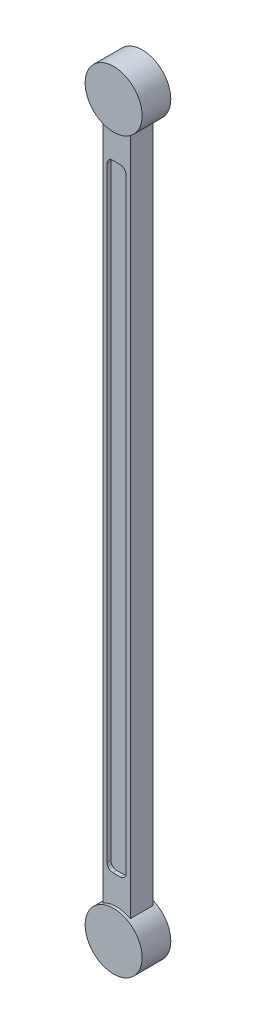
SolidWorks part; units mm, degrees
ref_plane "Front" through (0, 0, 0) normal (0, 0, 1) x (1, 0, 0)
ref_plane "Top" through (0, 0, 0) normal (0, 1, 0) x (1, 0, 0)
ref_plane "Right" through (0, 0, 0) normal (1, 0, 0) x (0, 0, -1)
sketch "Sketch1" plane through (-505.7052, -1154.2469, 0) normal (0, 0, 1) x (1, 0, 0)
  line L0 (486.1052, 2330.8055) -> (486.1052, 1197.687)
  line L1 (482.7052, 1195.9866) -> (482.7052, 2332.5059)
  line L2 (525.3052, 1197.687) -> (525.3052, 2330.8055)
  line L3 (528.7052, 2332.5059) -> (528.7052, 1195.9866)
  line L4 (486.2052, 1258.2462) -> (486.2052, 2330.7605)
  line L5 (489.7052, 2329.3546) -> (489.7052, 1258.2462)
  line L6 (499.7052, 2326.9677) -> (499.7052, 1258.2462)
  line L7 (511.7052, 1258.2462) -> (511.7052, 2326.9677)
  line L8 (521.7052, 1258.2462) -> (521.7052, 2329.3546)
  line L9 (525.2052, 2330.7605) -> (525.2052, 1258.2462)
  line L10 (486.2052, 1258.2462) -> (489.7052, 1258.2462)
  line L11 (525.2052, 1258.2462) -> (521.7052, 1258.2462)
  line L12 (511.7052, 1244.7462) -> (511.7052, 1248.2462)
  line L13 (499.7052, 1244.7462) -> (499.7052, 1248.2462)
  line L14 (511.7052, 1258.2462) -> (521.7052, 1258.2462)
  line L15 (499.7052, 1258.2462) -> (499.7052, 1248.2462)
  line L16 (511.7052, 1258.2462) -> (511.7052, 1248.2462)
  line L17 (499.7052, 1258.2462) -> (489.7052, 1258.2462)
  line L18 (499.7052, 1258.2462) -> (511.7052, 1258.2462)
  line L19 (511.7052, 1244.7462) -> (499.7052, 1244.7462)
  line L20 (499.7052, 1248.2462) -> (511.7052, 1248.2462)
  line L21 (499.7052, 2280.2462) -> (499.7052, 2283.7462)
  line L22 (489.7052, 2270.2462) -> (486.2052, 2270.2462)
  line L23 (511.7052, 2280.2462) -> (511.7052, 2283.7462)
  line L24 (521.7052, 2270.2462) -> (525.2052, 2270.2462)
  line L25 (521.7052, 2270.2462) -> (511.7052, 2270.2462)
  line L26 (511.7052, 2280.2462) -> (511.7052, 2270.2462)
  line L27 (499.7052, 2280.2462) -> (499.7052, 2270.2462)
  line L28 (489.7052, 2270.2462) -> (499.7052, 2270.2462)
  line L29 (499.7052, 2270.2462) -> (499.7052, 2244.371)
  line L30 (511.7052, 2270.2462) -> (499.7052, 2270.2462)
  line L31 (511.7052, 2257.0727) -> (511.7052, 2270.2462)
  line L32 (528.7052, 2277.7072) -> (528.7052, 2264.4354)
  line L33 (525.3052, 2264.9247) -> (525.3052, 2280.0122)
  line L34 (482.7052, 2234.556) -> (482.7052, 2308.8932)
  line L35 (486.1052, 2306.5882) -> (486.1052, 2236.519)
  line L36 (499.7052, 2283.7462) -> (511.7052, 2283.7462)
  line L37 (525.2052, 2270.2462) -> (525.2052, 2264.8669)
  line L38 (486.2052, 2236.5768) -> (486.2052, 2270.2462)
  line L39 (511.7052, 2280.2462) -> (499.7052, 2280.2462)
  line L40 (489.7052, 2270.2462) -> (489.7052, 2238.5975)
  line L41 (521.7052, 2262.8462) -> (521.7052, 2270.2462)
  line L42 (526.8021, 2265.7889) -> (527.2334, 2266.0379)
  line L43 (534.0206, 2434.9688) -> (531.9075, 2430.4373)
  circle A0 centre (505.7052, 1154.2462) radius 17.5
  circle A1 centre (505.7052, 1154.2462) radius 47.6577
  arc A2 (511.7052, 1244.7462) -> (525.2052, 1258.2462) centre (511.7052, 1258.2462) ccw
  arc A3 (486.2052, 1258.2462) -> (499.7052, 1244.7462) centre (499.7052, 1258.2462) ccw
  arc A4 (511.7052, 1248.2462) -> (521.7052, 1258.2462) centre (511.7052, 1258.2462) ccw
  arc A5 (489.7052, 1258.2462) -> (499.7052, 1248.2462) centre (499.7052, 1258.2462) ccw
  circle A6 centre (505.7052, 1154.2462) radius 22.5
  circle A7 centre (505.7052, 1154.2462) radius 27.5
  circle A8 centre (505.7052, 1154.2462) radius 16.5
  circle A9 centre (505.7052, 2374.2462) radius 47.6577
  circle A10 centre (505.7052, 2374.2462) radius 27.5
  circle A11 centre (505.7052, 2374.2462) radius 22.5
  arc A12 (499.7052, 2283.7462) -> (486.2052, 2270.2462) centre (499.7052, 2270.2462) ccw
  arc A13 (525.2052, 2270.2462) -> (511.7052, 2283.7462) centre (511.7052, 2270.2462) ccw
  arc A14 (521.7052, 2270.2462) -> (511.7052, 2280.2462) centre (511.7052, 2270.2462) ccw
  arc A15 (499.7052, 2280.2462) -> (489.7052, 2270.2462) centre (499.7052, 2270.2462) ccw
  circle A16 centre (505.7052, 2374.2462) radius 17.5
  circle A17 centre (505.7052, 2374.2462) radius 16.5
sketch "Sketch2" plane through (-505.7052, 0, 2556.1257) normal (0, 1, 0) x (1, 0, 0)
  line L0 (505.7052, 2532.1257) -> (505.7052, 2556.1257) construction
  line L1 (501.0475, 2580.6257) -> (549.0475, 2580.6257)
  line L2 (501.0475, 2580.6257) -> (501.0475, 2580.1257)
  line L3 (549.0475, 2580.1257) -> (549.0475, 2580.6257)
  line L4 (458.0475, 2575.1257) -> (458.0475, 2537.1257)
  line L5 (551.2498, 2580.1257) -> (463.0475, 2580.1257)
  line L6 (551.2498, 2532.1257) -> (551.434, 2532.1447)
  line L7 (551.434, 2532.1447) -> (551.6167, 2532.2017)
  line L8 (551.6167, 2532.2017) -> (551.7967, 2532.2961)
  line L9 (551.7967, 2532.2961) -> (551.9725, 2532.4272)
  line L10 (551.9725, 2532.4272) -> (552.1428, 2532.5942)
  line L11 (552.1428, 2532.5942) -> (552.3064, 2532.7956)
  line L12 (552.3064, 2532.7956) -> (552.4618, 2533.0299)
  line L13 (552.4618, 2533.0299) -> (552.6081, 2533.2955)
  line L14 (552.6081, 2533.2955) -> (552.744, 2533.5902)
  line L15 (552.744, 2533.5902) -> (552.8685, 2533.9118)
  line L16 (552.8685, 2533.9118) -> (552.9808, 2534.2578)
  line L17 (552.9808, 2534.2578) -> (553.0798, 2534.6257)
  line L18 (553.0798, 2534.6257) -> (553.1649, 2535.0126)
  line L19 (553.1649, 2535.0126) -> (553.2355, 2535.4156)
  line L20 (553.2355, 2535.4156) -> (553.2909, 2535.8316)
  line L21 (553.2909, 2535.8316) -> (553.3308, 2536.2575)
  line L22 (553.3308, 2536.2575) -> (553.3549, 2536.6899)
  line L23 (553.3549, 2536.6899) -> (553.3629, 2537.1257)
  line L24 (551.2498, 2532.1257) -> (463.0475, 2532.1257)
  line L25 (553.3629, 2575.1257) -> (458.0475, 2575.1257)
  line L26 (553.3629, 2575.1257) -> (553.3549, 2575.5615)
  line L27 (553.3549, 2575.5615) -> (553.3308, 2575.9939)
  line L28 (553.3308, 2575.9939) -> (553.2909, 2576.4198)
  line L29 (553.2909, 2576.4198) -> (553.2355, 2576.8358)
  line L30 (553.2355, 2576.8358) -> (553.1649, 2577.2388)
  line L31 (553.1649, 2577.2388) -> (553.0798, 2577.6257)
  line L32 (553.0798, 2577.6257) -> (552.9808, 2577.9936)
  line L33 (552.9808, 2577.9936) -> (552.8685, 2578.3396)
  line L34 (552.8685, 2578.3396) -> (552.744, 2578.6612)
  line L35 (552.744, 2578.6612) -> (552.6081, 2578.9559)
  line L36 (552.6081, 2578.9559) -> (552.4618, 2579.2215)
  line L37 (552.4618, 2579.2215) -> (552.3064, 2579.4558)
  line L38 (552.3064, 2579.4558) -> (552.1428, 2579.6572)
  line L39 (552.1428, 2579.6572) -> (551.9725, 2579.8242)
  line L40 (551.9725, 2579.8242) -> (551.7967, 2579.9553)
  line L41 (551.7967, 2579.9553) -> (551.6167, 2580.0497)
  line L42 (551.6167, 2580.0497) -> (551.434, 2580.1067)
  line L43 (551.434, 2580.1067) -> (551.2498, 2580.1257)
  line L44 (553.3629, 2537.1257) -> (553.3629, 2575.1257)
  line L45 (458.0475, 2537.1257) -> (553.3629, 2537.1257)
  line L46 (522.3697, 2530.8597) -> (522.8128, 2531.7094)
  line L47 (538.4272, 2528.1257) -> (522.8128, 2531.7094)
  line L48 (486.0475, 2524.2368) -> (486.4833, 2524.2516)
  line L49 (486.4833, 2524.2516) -> (486.9157, 2524.2959)
  line L50 (486.9157, 2524.2959) -> (487.3416, 2524.3693)
  line L51 (487.3416, 2524.3693) -> (487.7576, 2524.4713)
  line L52 (487.7576, 2524.4713) -> (488.1606, 2524.6012)
  line L53 (488.1606, 2524.6012) -> (488.5475, 2524.7578)
  line L54 (488.5475, 2524.7578) -> (488.9154, 2524.9401)
  line L55 (488.9154, 2524.9401) -> (489.2614, 2525.1466)
  line L56 (489.2614, 2525.1466) -> (489.583, 2525.3758)
  line L57 (489.583, 2525.3758) -> (489.8777, 2525.626)
  line L58 (489.8777, 2525.626) -> (490.1432, 2525.8951)
  line L59 (490.1432, 2525.8951) -> (490.3776, 2526.1813)
  line L60 (490.3776, 2526.1813) -> (490.579, 2526.4822)
  line L61 (490.579, 2526.4822) -> (490.7459, 2526.7956)
  line L62 (490.7459, 2526.7956) -> (490.8771, 2527.1192)
  line L63 (490.8771, 2527.1192) -> (490.9715, 2527.4504)
  line L64 (490.9715, 2527.4504) -> (491.0284, 2527.7868)
  line L65 (491.0284, 2527.7868) -> (491.0475, 2528.1257)
  line L66 (527.6129, 2528.1257) -> (496.0475, 2528.1257)
  line L67 (496.0475, 2528.1257) -> (491.0475, 2528.1257)
  line L68 (522.8128, 2531.7094) -> (522.552, 2532.1257)
  line L69 (538.4272, 2532.1257) -> (538.4272, 2528.1257)
  line L70 (496.0475, 2528.1257) -> (496.0475, 2532.1257)
  line L71 (458.0475, 2556.1257) -> (553.3629, 2556.1257) construction
  line L72 (505.7052, 2575.1257) -> (505.7052, 2700.0052) construction
  arc A0 (501.0475, 2580.6257) -> (502.984, 2581.1257) centre (501.0475, 2584.6257) ccw
  arc A1 (547.111, 2581.1257) -> (549.0475, 2580.6257) centre (549.0475, 2584.6257) ccw
  arc A2 (463.0475, 2580.1257) -> (458.0475, 2575.1257) centre (463.0475, 2575.1257) ccw
  arc A3 (458.0475, 2537.1257) -> (463.0475, 2532.1257) centre (463.0475, 2537.1257) ccw
  arc A4 (491.6106, 2532.2989) -> (486.0475, 2524.2368) centre (495.5173, 2523.6527) ccw
  arc A5 (522.3697, 2530.8597) -> (519.3677, 2532.1257) centre (513.1227, 2513.1257) ccw
  arc A6 (522.8128, 2531.7094) -> (520.3216, 2532.3493) centre (513.0839, 2499.0025) ccw
sketch "Sketch3" plane through (0, 0, 0) normal (0, 0, 1) x (1, 0, 0)
  line L0 (23, 1178.259) -> (23, 41.7397)
  line L2 (-23, 1178.259) -> (-23, 41.7397)
  arc A0 (-23, 41.7397) -> (23, 41.7397) centre (0, 0) ccw
  arc A1 (23, 1178.259) -> (-23, 1178.259) centre (0, 1219.9994) ccw
extrude "Extrude1" add sketch "Sketch3" against normal up to vertex and the other way blind 19.05 up to point (-47.6577, 0, -19)
sketch "Sketch4" plane through (0, 0, 19.05) normal (0, 0, 1) x (1, 0, 0)
  line L0 (-6, 93.9994) -> (6, 93.9994) construction
  line L1 (6, 1125.9994) -> (-6, 1125.9994) construction
  line L5 (15.888, 1178.259) -> (15.888, 41.7397)
  line L6 (15.888, 1116.3474) -> (15.888, 103.6514)
  line L7 (-6.236, 1125.9994) -> (6.236, 1125.9994)
  line L8 (-15.888, 41.7397) -> (-15.888, 1178.259)
  line L9 (-15.888, 103.6514) -> (-15.888, 1116.3474)
  line L10 (-6.236, 93.9994) -> (6.236, 93.9994)
  arc A0 (6.236, 93.9994) -> (15.888, 103.6514) centre (6.236, 103.6514) ccw
  arc A1 (-6.236, 93.9994) -> (-15.888, 103.6514) centre (-6.236, 103.6514) cw
  arc A2 (6.236, 1125.9994) -> (15.888, 1116.3474) centre (6.236, 1116.3474) cw
  arc A3 (-6.236, 1125.9994) -> (-15.888, 1116.3474) centre (-6.236, 1116.3474) ccw
  dimension "D3" = 9.652
  dimension "D1" = 7.112
  dimension "D2" = 7.112
extrude "Cut-Extrude1" cut sketch "Sketch4" against normal blind 6.35
sketch "Sketch5" plane through (0, 0, -19) normal (0, 0, -1) x (-1, 0, 0)
  line L4 (-15.888, 1116.3474) -> (-15.888, 103.6514)
  line L5 (6.236, 1125.9994) -> (-6.236, 1125.9994)
  line L6 (15.888, 103.6514) -> (15.888, 1116.3474)
  line L7 (-6.236, 93.9994) -> (6.236, 93.9994)
  line L8 (-15.888, 1116.3474) -> (-15.888, 103.6514)
  line L9 (6.236, 1125.9994) -> (-6.236, 1125.9994)
  line L10 (15.888, 103.6514) -> (15.888, 1116.3474)
  line L11 (-6.236, 93.9994) -> (6.236, 93.9994)
  arc A4 (-15.888, 103.6514) -> (-6.236, 93.9994) centre (-6.236, 103.6514) ccw
  arc A5 (-6.236, 1125.9994) -> (-15.888, 1116.3474) centre (-6.236, 1116.3474) ccw
  arc A6 (15.888, 1116.3474) -> (6.236, 1125.9994) centre (6.236, 1116.3474) ccw
  arc A7 (6.236, 93.9994) -> (15.888, 103.6514) centre (6.236, 103.6514) ccw
  arc A8 (-15.888, 103.6514) -> (-6.236, 93.9994) centre (-6.236, 103.6514) ccw
  arc A9 (-6.236, 1125.9994) -> (-15.888, 1116.3474) centre (-6.236, 1116.3474) ccw
  arc A10 (15.888, 1116.3474) -> (6.236, 1125.9994) centre (6.236, 1116.3474) ccw
  arc A11 (6.236, 93.9994) -> (15.888, 103.6514) centre (6.236, 103.6514) ccw
  dimension "D1" = 0
extrude "Cut-Extrude2" cut sketch "Sketch5" against normal blind 6.35
sketch "Sketch6" plane through (0, 0, 19.05) normal (0, 0, 1) x (1, 0, 0)
  circle A0 centre (0, 1219.9994) radius 47.6577
  circle A1 centre (0, 0) radius 47.6572
extrude "Extrude2" add sketch "Sketch6" along normal blind 4.826 and the other way blind 43.18
